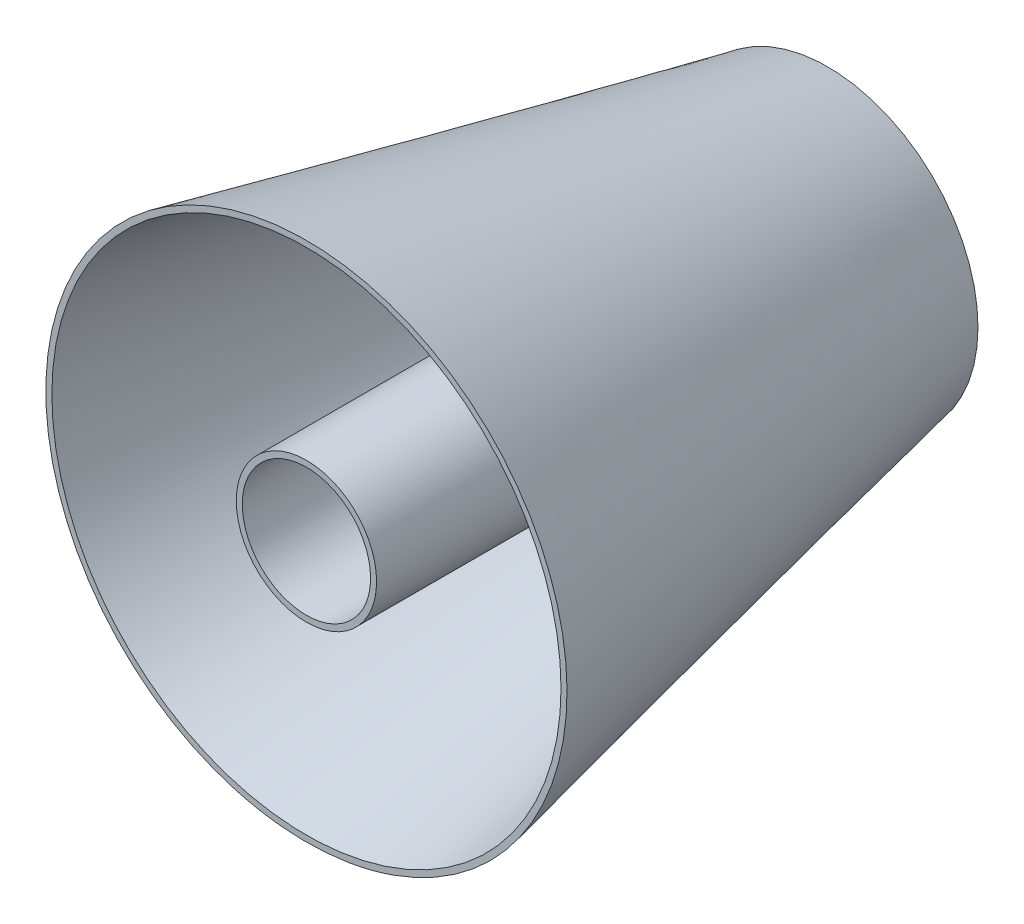
SolidWorks part; units mm, degrees
ref_plane "Front Plane" through (0, 0, 0) normal (0, 0, 1) x (1, 0, 0)
ref_plane "Top Plane" through (0, 0, 0) normal (0, 1, 0) x (1, 0, 0)
ref_plane "Right Plane" through (0, 0, 0) normal (1, 0, 0) x (0, 0, -1)
sketch "Sketch1" plane through (0, 0, 0) normal (0, 0, 1) x (1, 0, 0)
  circle A0 centre (0, 0) radius 75
ref_plane "Plane1" through (0, 0, 260) normal (0, 0, 1) x (1, 0, 0)
sketch "Sketch2" plane through (0, 0, 260) normal (0, 0, 1) x (1, 0, 0)
  circle A0 centre (0, 0) radius 130
loft "Loft1" add profiles "Sketch2", "Sketch1" connector at (-3.8385, 129.9433, 260) connector at (13.3586, 73.8007, 0)
sketch "Sketch3" plane through (0, 0, 0) normal (0, 0, -1) x (-1, 0, 0)
  circle A0 centre (0, 0) radius 72
sketch "Sketch4" plane through (0, 0, 260) normal (0, 0, 1) x (1, 0, 0)
  circle A0 centre (0, 0) radius 127
loft "Cut-Loft1" cut profiles "Sketch3", "Sketch4" connector at (-67.9404, 23.835, 0) connector at (-119.4919, 43.0197, 260)
sketch "Sketch5" plane through (0, 0, 0) normal (0, 0, -1) x (-1, 0, 0)
  circle A0 centre (0, 0) radius 73.4814
extrude "Boss-Extrude1" add sketch "Sketch5" against normal blind 3
sketch "Sketch6" plane through (0, 0, 3) normal (0, 0, 1) x (1, 0, 0)
  circle A0 centre (0, 0) radius 35
  circle A1 centre (0, 0) radius 32
extrude "Boss-Extrude2" add sketch "Sketch6" along normal blind 257
